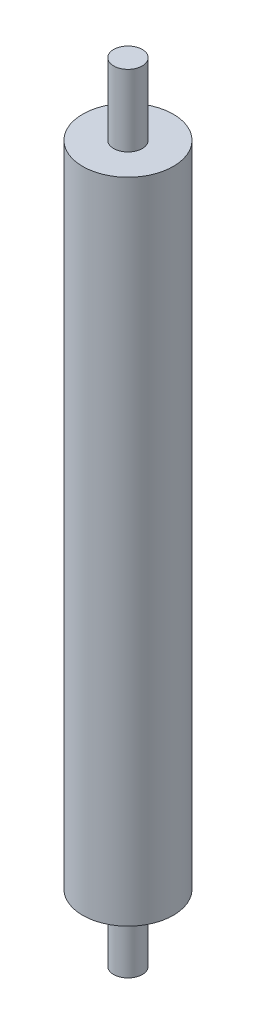
SolidWorks part; units mm, degrees
ref_plane "前视基准面" through (0, 0, 0) normal (0, 0, 1) x (1, 0, 0)
ref_plane "上视基准面" through (0, 0, 0) normal (0, 1, 0) x (1, 0, 0)
ref_plane "右视基准面" through (0, 0, 0) normal (1, 0, 0) x (0, 0, -1)
other "Configuration Table"
sketch "草图1" plane through (0, 0, 0) normal (0, 1, 0) x (1, 0, 0)
  circle A0 centre (0, 0) radius 1.9
  dimension "D1" = 3.8
extrude "凸台-拉伸2" add sketch "草图1" along normal blind 27.2
sketch "草图2" plane through (0, 27.2, 0) normal (0, 1, 0) x (1, 0, 0)
  circle A0 centre (0, 0) radius 0.6
  dimension "D1" = 1.2
extrude "凸台-拉伸3" add sketch "草图2" along normal blind 3 and the other way blind 30
